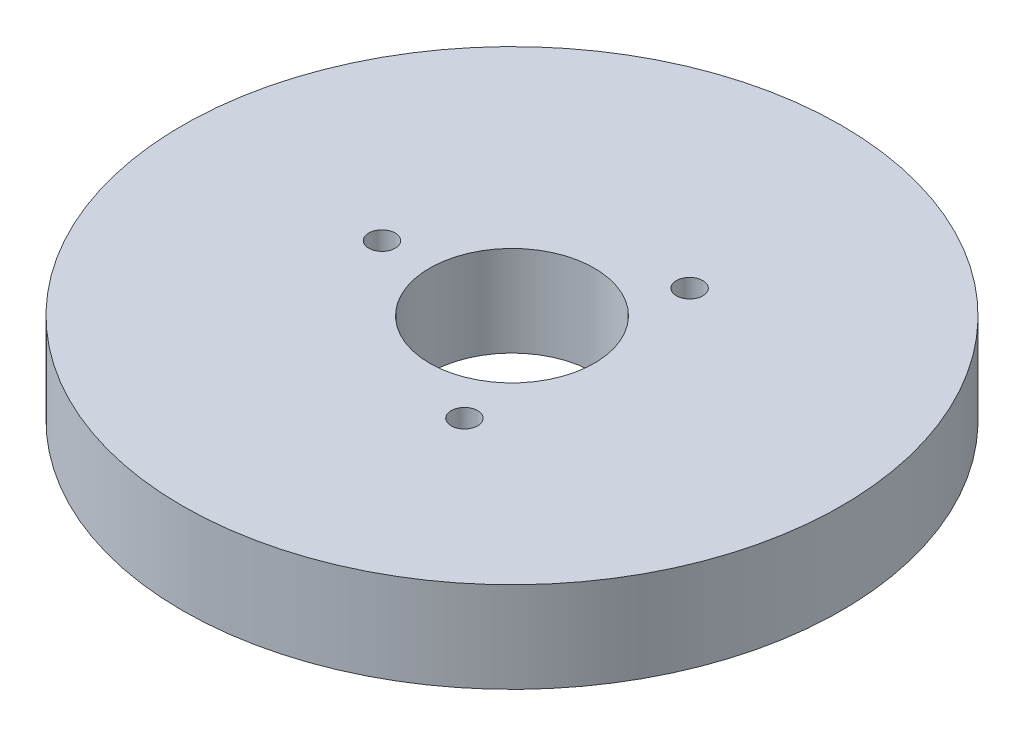
SolidWorks part; units mm, degrees
ref_plane "Front Plane" through (0, 0, 0) normal (0, 0, 1) x (1, 0, 0)
ref_plane "Top Plane" through (0, 0, 0) normal (0, 1, 0) x (1, 0, 0)
ref_plane "Right Plane" through (0, 0, 0) normal (1, 0, 0) x (0, 0, -1)
sketch "Sketch1" plane through (0, 0, 0) normal (0, 1, 0) x (1, 0, 0)
  circle A0 centre (0, 0) radius 40
  dimension "FLANGE_OD" = 80
extrude "Boss-Extrude1" add sketch "Sketch1" along normal blind 11
sketch "Sketch2" plane through (0, 0, 0) normal (0, 1, 0) x (1, 0, 0)
  circle A0 centre (0, 0) radius 10
  dimension "BORE_D" = 20
extrude "Cut-Extrude1" cut sketch "Sketch2" along normal through all
sketch "Sketch3" plane through (0, 11, 0) normal (0, 1, 0) x (1, 0, 0)
  circle A0 centre (0, 0) radius 15.7809 construction
  circle A1 centre (-15.7809, 0) radius 1.6048
  dimension "BOLT_D" = 3.2095
  dimension "BOLT_PCD" = 31.5617
extrude "Cut-Extrude2" cut sketch "Sketch3" against normal blind 8.6145
pattern_circular "CirPattern1" count 3 over 360 about axis through (0, 0, 0) along (0, 1, 0) of "Cut-Extrude2"
